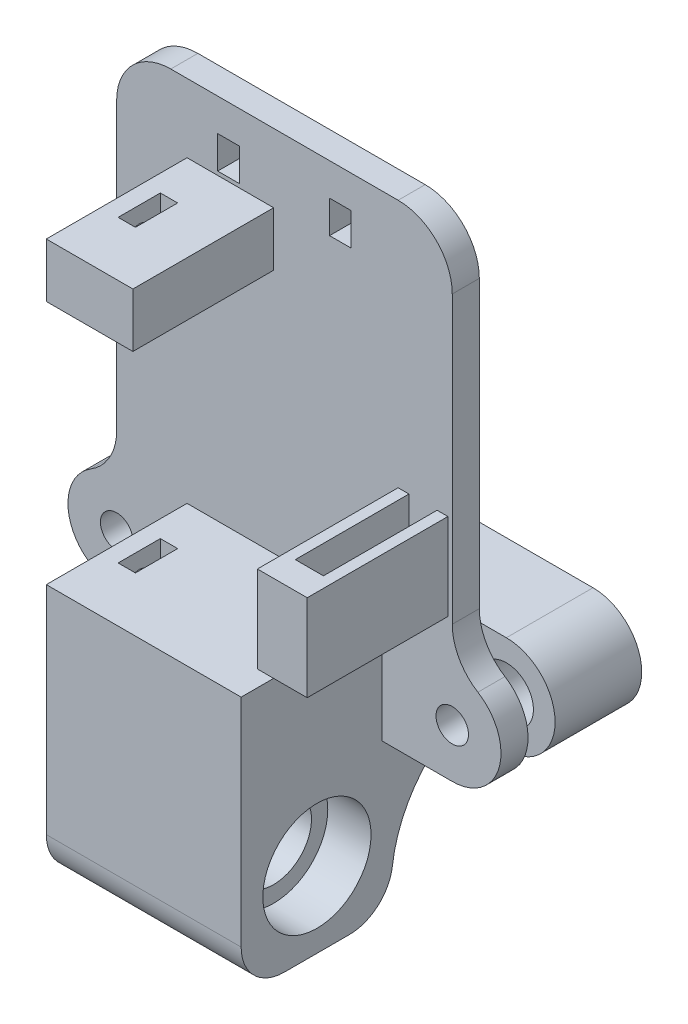
SolidWorks part; units mm, degrees
ref_plane "Alzado" through (0, 0, 0) normal (0, 0, 1) x (1, 0, 0)
ref_plane "Planta" through (0, 0, 0) normal (0, 1, 0) x (1, 0, 0)
ref_plane "Vista lateral" through (0, 0, 0) normal (1, 0, 0) x (0, 0, -1)
sketch "Croquis1" plane through (0, 0, 0) normal (0, 0, 1) x (1, 0, 0)
  line L0 (0, 15.8597) -> (0, -16.2083) construction
  line L1 (-15.5, 4.5) -> (15.5, 4.5)
  line L2 (-15.5, -4.5) -> (15.5, -4.5)
  circle A0 centre (-15.5, 0) radius 2.5
  arc A1 (-15.5, 4.5) -> (-15.5, -4.5) centre (-15.5, 0) ccw
  arc A2 (15.5, 4.5) -> (15.5, -4.5) centre (15.5, 0) cw
  circle A3 centre (15.5, 0) radius 2.5
  point P9 (0, 4.5)
  point P13 (0, -4.5)
  dimension "D2" = 5
  dimension "D3" = 2
  dimension "D1" = 15.5
extrude "Saliente-Extruir1" add sketch "Croquis1" along normal blind 28
sketch "Croquis6" plane through (0, 0, 28) normal (0, 0, 1) x (1, 0, 0)
  line L0 (-8, 2) -> (0, 2) construction
  line L1 (0, 2) -> (8, 2) construction
  line L2 (-8, 2) -> (0, 2)
  line L3 (0, 2) -> (8, 2)
  arc A0 (-20, 0) -> (-11.0654, -0.7646) centre (-15.5, 0) ccw construction
  arc A1 (11.0654, -0.7646) -> (20, 0) centre (15.5, 0) ccw construction
  arc A2 (-20, 0) -> (-11.0654, -0.7646) centre (-15.5, 0) ccw
  arc A3 (11.0654, -0.7646) -> (20, 0) centre (15.5, 0) ccw
  spline S0 degree 3 poles (904.451, 1776.4549) (-816.6838, -1874.9624) (652.4006, 1929.998) (-494.884, -1936.6009) knots -9.148222 -9.148222 -9.148222 -9.148222 9.909356 9.909356 9.909356 9.909356 only from (-11.0654, -0.7646) to (-8, 2) construction
  spline S1 degree 3 poles (494.8791, -1936.5843) (-652.3953, 1929.9831) (816.6783, -1874.9495) (-904.4458, 1776.4437) knots -8.909329 -8.909329 -8.909329 -8.909329 10.148203 10.148203 10.148203 10.148203 only from (8, 2) to (11.0654, -0.7646) construction
  spline S2 degree 3 poles (-11.0654, -0.7646) (-10.8733, 0.3499) (-9.5718, 2) (-8, 2) knots 0 0 0 0 1 1 1 1
  spline S3 degree 3 poles (8, 2) (9.5718, 2) (10.8733, 0.3499) (11.0654, -0.7646) knots 0 0 0 0 1 1 1 1
sketch "Croquis7" plane through (0, 0, 28) normal (0, 0, 1) x (1, 0, 0)
  line L0 (-15.5, -4.5) -> (15.5, -4.5) construction
  line L10 (10.4346, -1.2646) -> (10.4346, -4.5)
  line L11 (10.4346, -4.5) -> (-11.0654, -4.5)
  line L13 (0, 1.5) -> (7.3691, 1.5)
  line L14 (-8, 1.5) -> (0, 1.5)
  line L15 (-11.0654, -1.2646) -> (-11.0654, -4.5)
  spline S12 degree 3 poles (7.3691, 1.5) (8.9409, 1.5) (10.2424, -0.1501) (10.4346, -1.2646) knots 0 0 0 0 1 1 1 1
  spline S13 degree 3 poles (-11.0654, -1.2646) (-10.8733, -0.1501) (-9.5718, 1.5) (-8, 1.5) knots 0 0 0 0 1 1 1 1
  dimension "D1" = 6
  dimension "D2" = 21.5
extrude "Saliente-Extruir3" add sketch "Croquis7" along normal blind 2.5
sketch "Croquis8" plane through (0, 0, 30.5) normal (0, 0, 1) x (1, 0, 0)
  line L2 (15.5, 4.5) -> (15.5, 39.5)
  line L3 (15.5, 39.5) -> (-15.5, 39.5)
  line L4 (-15.5, 4.5) -> (-15.5, 39.5)
  line L7 (15.5, -4.5) -> (-15.5, -4.5)
  circle A2 centre (15.5, 0) radius 1.5
  circle A3 centre (-15.5, 0) radius 1.5
  arc A6 (15.5, -4.5) -> (15.5, 4.5) centre (15.5, 0) ccw
  arc A7 (-15.5, 4.5) -> (-15.5, -4.5) centre (-15.5, 0) ccw
  dimension "D1" = 3
  dimension "D2" = 3
  dimension "D3" = 35
extrude "Saliente-Extruir4" add sketch "Croquis8" along normal blind 2.5
sketch "Croquis9" plane through (0, 0, 33) normal (0, 0, 1) x (1, 0, 0)
  line L0 (-15.5, -4.5) -> (15.5, -4.5) construction
  line L1 (9, -4.5) -> (-9, -4.5)
  line L2 (9, -4.5) -> (9, 5.5)
  line L3 (9, 5.5) -> (-9, 5.5)
  line L4 (-9, -4.5) -> (-9, 5.5)
  point P6 (0, -4.5)
  point P7 (0, -4.5)
  dimension "D1" = 18
  dimension "D2" = 10
extrude "Saliente-Extruir5" add sketch "Croquis9" along normal blind 13
sketch "Croquis3" plane through (0, -4.5, 0) normal (0, -1, 0) x (1, 0, 0)
  line L1 (-9, 46) -> (9, 46)
  line L2 (-9, 46) -> (-9, 32)
  line L3 (-9, 32) -> (9, 32)
  line L4 (9, 46) -> (9, 32)
  line L5 (-9, 46) -> (9, 46) construction
  line L6 (-15.5, 0) -> (15.5, 0) construction
  point P4 (0, 32)
  point P10 (0, 0)
  dimension "D1" = 18
  dimension "D2" = 14
extrude "Saliente-Extruir2" add sketch "Croquis3" along normal blind 14
sketch "Croquis4" plane through (-9, 0, 0) normal (-1, 0, 0) x (0, 0, 1)
  line L1 (46, -18.5) -> (32, -18.5) construction
  line L2 (46, -18.5) -> (32, -18.5) construction
  circle A0 centre (39, -11.5) radius 5
  point P8 (39, -18.5)
  dimension "D1" = 10
  dimension "D2" = 7
extrude "Cortar-Extruir1" cut sketch "Croquis4" against normal blind 4
extrude "Cortar-Extruir2" cut sketch "Croquis4<2>" along normal blind 4 from surface starting at face at (9, -5.8333, 37)
sketch "Croquis4<2>" plane through (-9, 0, 0) normal (-1, 0, 0) x (0, 0, 1) same geometry as "Croquis4"
sketch "Croquis5" plane through (-5, 0, 0) normal (-1, 0, 0) x (0, 0, 1)
  circle A0 centre (39, -11.5) radius 3.5
  dimension "D1" = 7
extrude "Cortar-Extruir3" cut sketch "Croquis5" against normal up to next
fillet "Redondeo1" radius 4 2 edges at (0, -18.5, 32) (0, -18.5, 46)
sketch "Croquis10" plane through (0, 0, 0) normal (0, 0, -1) x (-1, 0, 0)
  line L0 (15.5, -4.5) -> (-15.5, -4.5) construction
  line L1 (15.5, 4.5) -> (-15.5, 4.5) construction
  line L3 (20, -4.5) -> (-20, -4.5)
  line L4 (20, -4.5) -> (20, 4.5)
  line L5 (20, 4.5) -> (-20, 4.5)
  line L6 (-20, -4.5) -> (-20, 4.5)
  arc A0 (15.5, 4.5) -> (15.5, -4.5) centre (15.5, 0) ccw construction
  arc A1 (-15.5, -4.5) -> (-15.5, 4.5) centre (-15.5, 0) ccw construction
extrude "Cortar-Extruir4" cut sketch "Croquis10" against normal blind 20
sketch "Croquis11" plane through (0, 0, 33) normal (0, 0, 1) x (1, 0, 0)
  line L0 (9, 5.5) -> (-9, 5.5) construction
  line L1 (-9, 28.15) -> (-1, 28.15)
  line L2 (-9, 28.15) -> (-9, 33.15)
  line L3 (-9, 33.15) -> (-1, 33.15)
  line L4 (-1, 28.15) -> (-1, 33.15)
  line L5 (-9, 5.5) -> (-9, -4.5) construction
  dimension "D1" = 22.65
  dimension "D2" = 5
  dimension "D3" = 8
extrude "Saliente-Extruir6" add sketch "Croquis11" along normal up to vertex (13 mm away) up to point (-9, -14.5, 46)
sketch "Croquis12" plane through (-9, 0, 0) normal (-1, 0, 0) x (0, 0, 1)
  line L0 (33, 5.5) -> (33, -4.5) construction
  line L1 (46, 5.5) -> (33, 5.5) construction
  line L2 (46, 28.15) -> (46, 5.5) construction
  line L3 (46, 16.825) -> (32.0777, 16.825) construction
  circle A0 centre (39, 3) radius 1
  circle A1 centre (39, 30.65) radius 1
  dimension "D3" = 2
  dimension "D1" = 6
  dimension "D2" = 2.5
extrude "Cortar-Extruir5" cut sketch "Croquis12" against normal blind 6
sketch "Croquis13" plane through (0, 33.15, 0) normal (0, 1, 0) x (1, 0, 0)
  line L0 (-1, -33) -> (-9, -33) construction
  line L1 (-5.815, -40.95) -> (-7.415, -40.95)
  line L2 (-5.815, -40.95) -> (-5.815, -37.05)
  line L3 (-5.815, -37.05) -> (-7.415, -37.05)
  line L4 (-7.415, -40.95) -> (-7.415, -37.05)
  point P6 (-7.415, -39)
  dimension "D1" = 6
  dimension "D2" = 1.6
  dimension "D3" = 3.9
extrude "Cortar-Extruir6" cut sketch "Croquis13" against normal blind 33
fillet "Redondeo2" radius 5 4 edges at (-15.5, 4.5, 31.75) (15.5, 4.5, 31.75) (15.5, 39.5, 31.75) (-15.5, 39.5, 31.75)
fillet "Redondeo3" radius 12 1 edges at (0, -4.5, 32)
sketch "Croquis14" plane through (0, 5.5, 0) normal (0, 1, 0) x (1, 0, 0)
  line L0 (10.5, -33) -> (10.5, -46)
  line L1 (10.5, -33) -> (-10.5, -33) construction
  line L2 (10.5, -46) -> (15.1, -46)
  line L3 (15.1, -46) -> (15.1, -33)
  line L4 (15.1, -33) -> (14.1, -33)
  line L5 (15.5, -33) -> (17.8684, -33) construction
  line L6 (14.1, -33) -> (14.1, -43.5)
  line L7 (14.1, -43.5) -> (11.5, -43.5)
  line L8 (11.5, -43.5) -> (11.5, -33)
  line L9 (10.5, -33) -> (15.5, -33) construction
  line L10 (11.5, -33) -> (10.5, -33)
  line L11 (9, -46) -> (9, -33) construction
  dimension "D1" = 1.5
  dimension "D2" = 1
  dimension "D3" = 1
  dimension "D4" = 2.6
  dimension "D5" = 10.5
extrude "Saliente-Extruir7" add sketch "Croquis14" along normal blind 8 from offset 3
sketch "Croquis15" plane through (0, 0, 30.5) normal (0, 0, -1) x (-1, 0, 0)
  line L0 (-4.166, 55.9488) -> (-4.166, 18.1044) construction
  line L1 (4.166, 18.1044) -> (4.166, 55.9488) construction
  line L2 (-4.166, 55.9488) -> (-4.166, 18.1044)
  line L3 (4.166, 18.1044) -> (4.166, 55.9488)
sketch "Croquis16" plane through (0, 0, 30.5) normal (0, 0, -1) x (-1, 0, 0)
  line L0 (-4.166, 55.9488) -> (-4.166, 18.1044) construction
  line L1 (-4.166, 36.5) -> (-6.166, 36.5)
  line L2 (-4.166, 36.5) -> (-4.166, 33.5)
  line L3 (-4.166, 33.5) -> (-6.166, 33.5)
  line L4 (-6.166, 36.5) -> (-6.166, 33.5)
  line L5 (-10.5, 39.5) -> (10.5, 39.5) construction
  line L6 (0, 39.5) -> (0, 32.1473) construction
  line L7 (6.166, 36.5) -> (6.166, 33.5)
  line L8 (4.166, 33.5) -> (6.166, 33.5)
  line L9 (4.166, 36.5) -> (4.166, 33.5)
  line L10 (4.166, 36.5) -> (6.166, 36.5)
  dimension "D1" = 2
  dimension "D2" = 3
  dimension "D3" = 3
extrude "Cortar-Extruir7" cut sketch "Croquis16" against normal up to vertex (2.5 mm away) up to point (-10.5, 39.5, 33)
